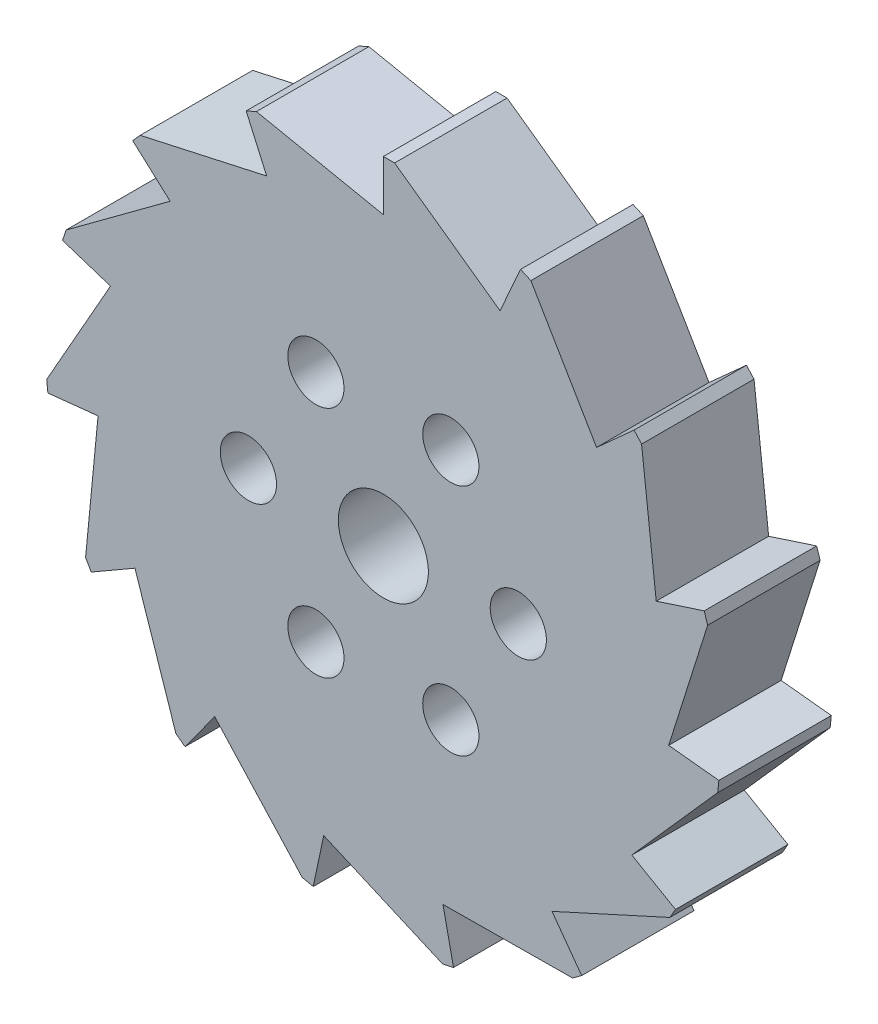
SolidWorks part; units mm, degrees
ref_plane "Front Plane" through (0, 0, 0) normal (0, 0, 1) x (1, 0, 0)
ref_plane "Top Plane" through (0, 0, 0) normal (0, 1, 0) x (1, 0, 0)
ref_plane "Right Plane" through (0, 0, 0) normal (1, 0, 0) x (0, 0, -1)
sketch "Sketch1" plane through (0, 0, 0) normal (0, 0, 1) x (1, 0, 0)
  line L0 (0, 25.5126) -> (0, 30)
  line L1 (0, 30) -> (1.0009, 30)
  line L2 (1.0009, 30) -> (10.3769, 23.307)
  line L3 (13.1165, 26.9993) -> (18.9596, 17.0713)
  line L4 (10.3769, 23.307) -> (12.2021, 27.4064)
  line L5 (12.2021, 27.4064) -> (13.1165, 26.9993)
  line L6 (22.9641, 19.3301) -> (24.264, 7.8838)
  line L7 (18.9596, 17.0713) -> (22.2943, 20.0739)
  line L8 (22.2943, 20.0739) -> (22.9641, 19.3301)
  line L9 (28.841, 8.3186) -> (25.3729, -2.6668)
  line L10 (24.264, 7.8838) -> (28.5317, 9.2705)
  line L11 (28.5317, 9.2705) -> (28.841, 8.3186)
  line L12 (29.731, -4.1313) -> (22.0946, -12.7563)
  line L13 (25.3729, -2.6668) -> (29.8357, -3.1359)
  line L14 (29.8357, -3.1359) -> (29.731, -4.1313)
  line L15 (25.4803, -15.8668) -> (14.996, -20.6402)
  line L16 (22.0946, -12.7563) -> (25.9808, -15)
  line L17 (25.9808, -15) -> (25.4803, -15.8668)
  line L18 (16.8238, -24.8588) -> (5.3044, -24.9551)
  line L19 (14.996, -20.6402) -> (17.6336, -24.2705)
  line L20 (17.6336, -24.2705) -> (16.8238, -24.8588)
  line L21 (5.2583, -29.5525) -> (-5.3044, -24.9551)
  line L22 (5.3044, -24.9551) -> (6.2374, -29.3444)
  line L23 (6.2374, -29.3444) -> (5.2583, -29.5525)
  line L24 (-7.2164, -29.1363) -> (-14.996, -20.6402)
  line L25 (-5.3044, -24.9551) -> (-6.2374, -29.3444)
  line L26 (-6.2374, -29.3444) -> (-7.2164, -29.1363)
  line L27 (-18.4433, -23.6822) -> (-22.0946, -12.7563)
  line L28 (-14.996, -20.6402) -> (-17.6336, -24.2705)
  line L29 (-17.6336, -24.2705) -> (-18.4433, -23.6822)
  line L30 (-26.4812, -14.1332) -> (-25.3729, -2.6668)
  line L31 (-22.0946, -12.7563) -> (-25.9808, -15)
  line L32 (-25.9808, -15) -> (-26.4812, -14.1332)
  line L33 (-29.9403, -2.1404) -> (-24.264, 7.8838)
  line L34 (-25.3729, -2.6668) -> (-29.8357, -3.1359)
  line L35 (-29.8357, -3.1359) -> (-29.9403, -2.1404)
  line L36 (-28.2224, 10.2224) -> (-18.9596, 17.0713)
  line L37 (-24.264, 7.8838) -> (-28.5317, 9.2705)
  line L38 (-28.5317, 9.2705) -> (-28.2224, 10.2224)
  line L39 (-21.6246, 20.8177) -> (-10.3769, 23.307)
  line L40 (-18.9596, 17.0713) -> (-22.2943, 20.0739)
  line L41 (-22.2943, 20.0739) -> (-21.6246, 20.8177)
  line L42 (-11.2877, 27.8135) -> (0, 25.5126)
  line L43 (-10.3769, 23.307) -> (-12.2021, 27.4064)
  line L44 (-12.2021, 27.4064) -> (-11.2877, 27.8135)
  line L45 (0, 0) -> (14.3091, 20.5) construction
  circle A0 centre (0, 0) radius 25 construction
  circle A1 centre (0, 0) radius 4
  dimension "D1" = 50
  dimension "D8" = 8
  dimension "D2" = 4.4874
  dimension "D3" = 1.0009
  dimension "D4" = 25.5126
  dimension "D6" = 25
  dimension "D7" = 10.3769
  dimension "D5" = 15
extrude "Boss-Extrude2" add sketch "Sketch1" along normal blind 10 contours L9 L13 L14 L12 L16 L17 L15 L19 L20 L18 L22 L23 L21 L25 L26 L24 L28 L29 L27 L31 L32 L30 L34 L35 L33 L37 L38 L36 L40 L41 L39 L43 L44 L42 L0 L1 L2 L4 L5 L3 L7 L8 L6 L10 L11
sketch "Sketch2" plane through (0, 0, 0) normal (0, 0, -1) x (-1, 0, 0)
  circle A0 centre (0, 0) radius 4
  circle A2 centre (-12, 0) radius 2.5
  circle A3 centre (-6, 10.3923) radius 2.5
  circle A4 centre (6, 10.3923) radius 2.5
  circle A5 centre (12, 0) radius 2.5
  circle A6 centre (6, -10.3923) radius 2.5
  circle A7 centre (-6, -10.3923) radius 2.5
  point P18 (0, 0)
  dimension "D1" = 8
  dimension "D3" = 12
  dimension "D2" = 5
  dimension "D4" = 6
extrude "Cut-Extrude1" cut sketch "Sketch2" against normal blind 10
